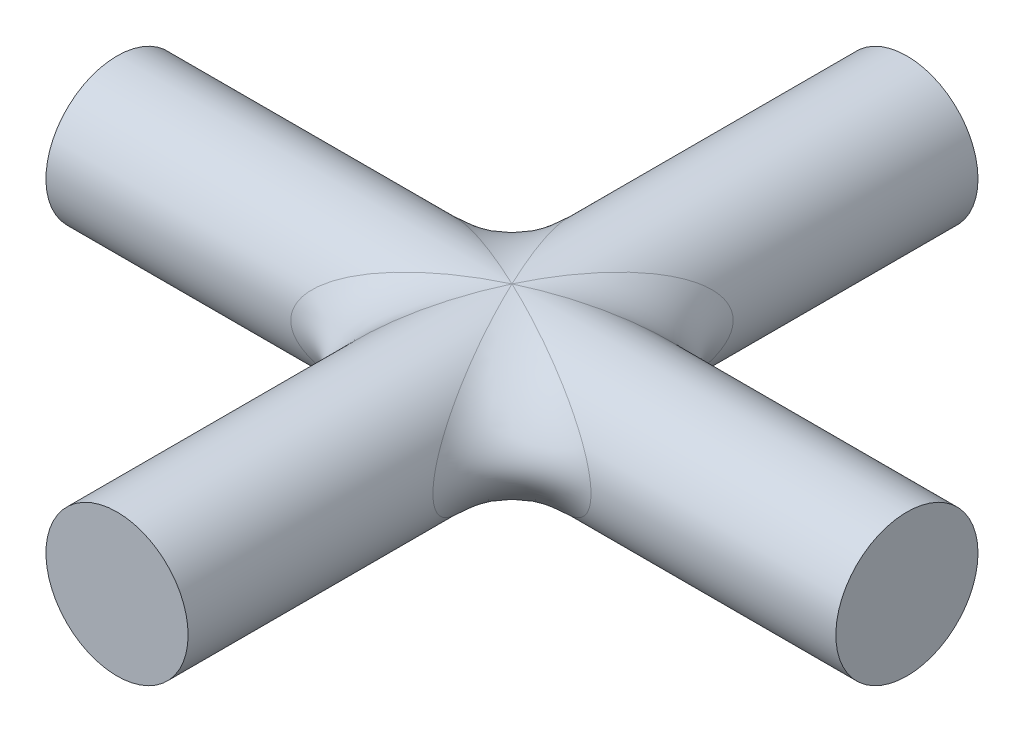
SolidWorks part; units mm, degrees
material "Plain Carbon Steel"
ref_plane "Front XY" through (0, 0, 0) normal (0, 0, 1) x (1, 0, 0)
ref_plane "Top XZ" through (0, 0, 0) normal (0, 1, 0) x (1, 0, 0)
ref_plane "Right YZ" through (0, 0, 0) normal (1, 0, 0) x (0, 0, -1)
sketch "Sketch1" plane through (0, 0, 0) normal (1, 0, 0) x (0, 0, -1)
  circle A0 centre (0, 0) radius 2.286
  dimension "D1" = 4.572
extrude "Boss-Extrude1" add sketch "Sketch1" along normal mid plane 25.4 contours A0
sketch "Sketch2" plane through (0, 0, 0) normal (0, 0, 1) x (1, 0, 0)
  circle A0 centre (0, 0) radius 2.286
  dimension "D1" = 4.572
extrude "Boss-Extrude2" add sketch "Sketch2" along normal mid plane 25.4
fillet "Fillet1" radius 2.54 4 edges at (2.286, 0, 2.286) (-2.286, 0, 2.286) (-2.286, 0, -2.286) (2.286, 0, -2.286)
